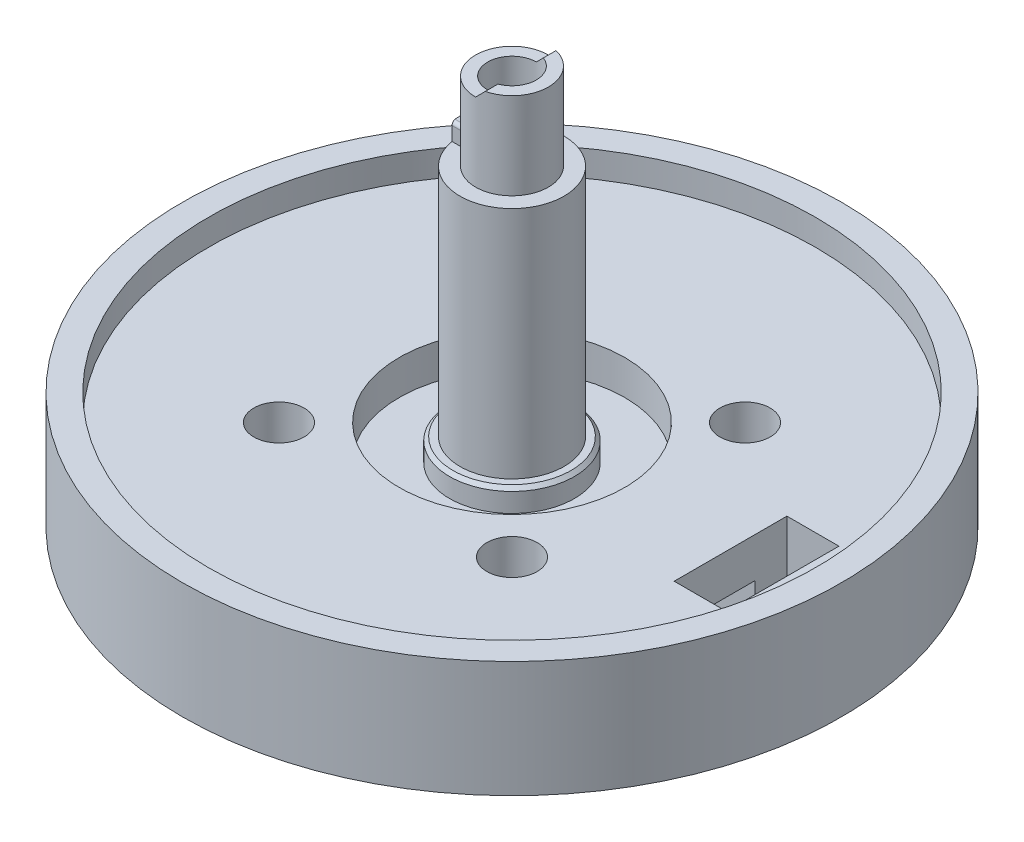
SolidWorks part; units mm, degrees
ref_plane "前视基准面" through (0, 0, 0) normal (0, 0, 1) x (1, 0, 0)
ref_plane "上视基准面" through (0, 0, 0) normal (0, 1, 0) x (1, 0, 0)
ref_plane "右视基准面" through (0, 0, 0) normal (1, 0, 0) x (0, 0, -1)
sketch "草图1" plane through (0, 0, 0) normal (0, 0, 1) x (1, 0, 0)
  line L0 (0, 0) -> (0, 22.2201) construction
  line L1 (-3, 12.8) -> (-2.1, 12.8)
  line L2 (-2.1, 12.8) -> (-2.1, 17.8)
  line L3 (-2.1, 17.8) -> (-1.4, 17.8)
  line L4 (-1.4, 17.8) -> (-1.4, -2.6859)
  line L6 (-3, -0.7) -> (-3, 12.8)
  line L7 (-19, 1.5) -> (-17.5, 1.5)
  line L8 (-17.5, 1.5) -> (-17.5, 0)
  line L9 (-17.5, 0) -> (-6.5, 0)
  line L10 (-6.5, 0) -> (-6.5, -2)
  line L13 (-19, 1.5) -> (-19, -5.2)
  line L14 (-19, -5.2) -> (-1.4, -5.2)
  line L15 (-1.4, -5.2) -> (-1.4, -2.6859)
  line L16 (-21.0007, 0) -> (21.0007, 0) construction
  line L18 (0, 0) -> (0, -7.9329) construction
  line L19 (-3, -0.7) -> (-3.6, -0.7)
  line L20 (-3.6, -0.7) -> (-3.6, -2)
  line L21 (-3.6, -2) -> (-6.5, -2)
  point P19 (0, 0)
  point P24 (-2.55, 12.8)
  dimension "D1" = 6
  dimension "D2" = 2.8
  dimension "D3" = 5
  dimension "D4" = 35
  dimension "D5" = 13
  dimension "D6" = 2
  dimension "D7" = 5.2
  dimension "D8" = 1.5
  dimension "D9" = 0.7
  dimension "D10" = 12.8
  dimension "D11" = 1.5
  dimension "D12" = 1.3
  dimension "D13" = 7.2
revolve "旋转3" add sketch "草图1" angle 360 about L0
sketch "草图3" plane through (0, 17.8, 0) normal (0, 1, 0) x (1, 0, 0)
  line L0 (0, 0) -> (-3.9693, 0) construction
  line L2 (-3.2821, 0.5) -> (-1, 0.5)
  line L3 (-3.2821, 0.5) -> (-3.2821, -0.5)
  line L4 (-3.2821, -0.5) -> (-1, -0.5)
  line L5 (-1, 0.5) -> (-1, -0.5)
  circle A1 centre (0, 0) radius 3
  circle A2 centre (0, 0) radius 3
  circle M6 centre (0, 0) radius 2.1
  dimension "D1" = 1
  dimension "D2" = 2.2821
  dimension "D3" = 1
  dimension "D4" = 0
extrude "凸台-拉伸1" add sketch "草图3" along normal blind 1 from surface contours L0 L2 A2 M6 | L0 A2 L4 M6 region at (-2.5329, 17.8, 0.2508) region at (-2.5329, 17.8, -0.2508) starting at face at (0, 12.8, -3)
fillet "圆角1" radius 0.2 2 edges at (-2.4988, 13.8, 0.5) (-2.4988, 13.8, -0.5)
sketch "草图4" plane through (0, -5.2, 0) normal (0, -1, 0) x (1, 0, 0)
  line L0 (0, 0) -> (21.9958, 0) construction
  line L1 (12.6, -3.25) -> (15.6, -3.25)
  line L2 (12.6, -3.25) -> (12.6, 3.25)
  line L3 (12.6, 3.25) -> (15.6, 3.25)
  line L4 (15.6, -3.25) -> (15.6, 3.25)
  dimension "D1" = 3
  dimension "D2" = 6.5
  dimension "D3" = 12.6
extrude "切除-拉伸1" cut sketch "草图4" against normal up to next
sketch "草图6" plane through (0, -5.2, 0) normal (0, -1, 0) x (1, 0, 0)
  line L0 (-23.0962, 0) -> (23.0962, 0) construction
  line L1 (6.7175, 6.7175) -> (-6.7175, -6.7175) construction
  line L3 (0, 26.4551) -> (0, -26.4551) construction
  point P4 (0, 0)
  point P5 (0, 0)
  point P8 (-6.7175, 6.7175)
  point P9 (0, 0)
  point P10 (-6.7175, -6.7175)
  point P11 (6.7175, -6.7175)
  point P12 (6.7175, 6.7175)
  point P16 (0, 0)
  dimension "D1" = 19
  dimension "D2" = 45
hole_wizard "Ø2.9 (2.9) 直径孔1" positions "草图7" profile "草图8" hole size "Ø2.9" standard "GB" end condition up to next
sketch "草图7" plane through (0, -5.2, 0) normal (0, -1, 0) x (-1, 0, 0)
  point P0 (-6.7175, 6.7175)
  point P3 (6.7175, 6.7175)
  point P6 (6.7175, -6.7175)
  point P9 (-6.7175, -6.7175)
sketch "草图8" plane through (6.7175, -5.2, -6.7175) normal (1, 0, 0) x (0, 0, -1)
  line L0 (0, 0) -> (0, 5.2)
  line L1 (0, 5.2) -> (1.45, 5.2)
  line L2 (1.45, 5.2) -> (1.45, 0)
  line L5 (1.45, 0) -> (0, 0)
  line L11 (0, -6.35) -> (0, 107.95) construction
  dimension "通孔孔直径" = 2.9
  dimension "通孔孔深度" = 5.2
sketch "草图9" plane through (0, -5.2, 0) normal (0, -1, 0) x (1, 0, 0)
  line L1 (-3.25, 2.75) -> (3.25, 2.75)
  line L2 (-3.25, 2.75) -> (-3.25, -2.75)
  line L3 (-3.25, -2.75) -> (3.25, -2.75)
  line L4 (3.25, 2.75) -> (3.25, -2.75)
  line L6 (-23.0962, 0) -> (23.0962, 0) construction
  line L7 (0, 26.4551) -> (0, -26.4551) construction
  line L8 (-23.0962, 0) -> (23.0962, 0) construction
  line L9 (0, 26.4551) -> (0, -26.4551) construction
  dimension "D1" = 6.5
  dimension "D2" = 5.5
extrude "切除-拉伸2" cut sketch "草图9" against normal blind 1.9
sketch "草图10" plane through (0, -5.2, 0) normal (0, -1, 0) x (1, 0, 0)
  line L0 (-23.0962, 0) -> (23.0962, 0) construction
  line L1 (-23.0962, 0) -> (23.0962, 0) construction
  line L2 (12.6, 3.25) -> (12.6, -3.25) construction
  line L3 (0, 1.4) -> (12.6, 1.4)
  line L4 (0, 1.4) -> (0, -1.4)
  line L5 (0, -1.4) -> (12.6, -1.4)
  line L6 (12.6, 1.4) -> (12.6, -1.4)
  circle A0 centre (0, 0) radius 1.4 construction
  circle A3 centre (0, 0) radius 1.4 construction
extrude "切除-拉伸3" cut sketch "草图10" against normal offset from surface (2.9 mm away) 1 up to face at (0, -3.3, 0) offset beyond the face yes
chamfer "倒角1" distance 1 angle 45 3 edges at (3.25, -3.3, -2.075) (3.25, -3.3, 2.075) (-3.25, -3.3, 0)
chamfer "倒角2" distance 0.2 angle 45 1 edges at (0, -0.7, -3.6)
sketch "草图11" plane through (0, 17.8, 0) normal (0, 1, 0) x (1, 0, 0)
  line L0 (0, -26.4551) -> (0, 26.4551) construction
  line L1 (0, 2.1) -> (-2.2966, 2.1)
  line L2 (0, 2.1) -> (0, -2.1)
  line L3 (0, -2.1) -> (-2.2966, -2.1)
  line L4 (-2.2966, 2.1) -> (-2.2966, -2.1)
  circle A0 centre (0, 0) radius 2.1 construction
  point P8 (0, -2.0974)
extrude "切除-拉伸4" cut sketch "草图11" against normal blind 0.5
chamfer "倒角3" distance 0.5 angle 45 2 edges at (0, 17.8, 1.75) (0, 17.8, -1.75)
